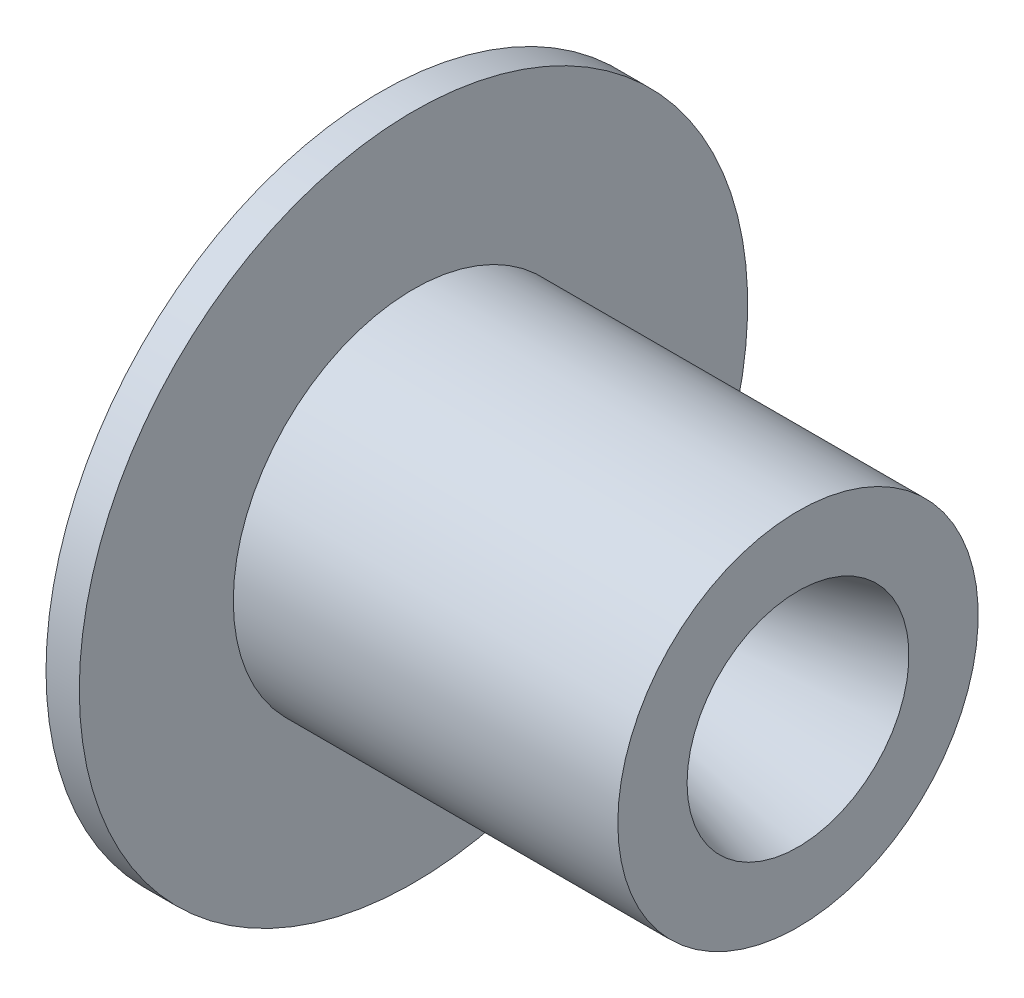
SolidWorks part; units mm, degrees
ref_plane "Front Plane" through (0, 0, 0) normal (0, 0, 1) x (1, 0, 0)
ref_plane "Top Plane" through (0, 0, 0) normal (0, 1, 0) x (1, 0, 0)
ref_plane "Right Plane" through (0, 0, 0) normal (1, 0, 0) x (0, 0, -1)
sketch "Sketch1" plane through (0, 0, 0) normal (0, 0, 1) x (1, 0, 0)
  line L20 (-1.458, 2.4752) -> (32.997, 2.4752) construction
  line L33 (20, 9.4212) -> (26.5, 9.4212)
  line L34 (20, 9.4212) -> (0, 27.8752)
  line L37 (0, 27.8752) -> (0, 53.4752)
  line L38 (0, 53.4752) -> (5.08, 53.4752)
  line L39 (5.08, 53.4752) -> (5.08, 29.9752)
  line L43 (63.7608, 29.9752) -> (63.7608, 19.4052)
  line L52 (63.7608, 19.4052) -> (26.5, 9.4212)
  line L53 (63.7608, 29.9752) -> (5.08, 29.9752)
  point P0 (-1.458, 2.4752)
  point P1 (2.54, 53.4752)
  point P12 (20, 9.4212)
  point P24 (26.5, 9.4212)
  dimension "D1" = 6.946
  dimension "D2" = 25.4
  dimension "D5" = 5.08
  dimension "D7" = 20
  dimension "D10" = 15
  dimension "D8" = 16.93
  dimension "D3" = 27.5
  dimension "D4" = 51
  dimension "D6" = 6.5
revolve "Nozzle" add sketch "Sketch1" angle 360 about L20
sketch "Sketch3" plane through (0, 0, 0) normal (-1, 0, 0) x (0, 0, 1)
  circle A0 centre (0, 42.4802) radius 3.3
  circle A1 centre (0, 2.4752) radius 51 construction
  circle A2 centre (28.2878, 30.763) radius 3.3
  circle A3 centre (40.005, 2.4752) radius 3.3
  circle A4 centre (28.2878, -25.8126) radius 3.3
  circle A5 centre (0, -37.5298) radius 3.3
  circle A6 centre (-28.2878, -25.8126) radius 3.3
  circle A7 centre (-40.005, 2.4752) radius 3.3
  circle A8 centre (-28.2878, 30.763) radius 3.3
  circle A13 centre (0, 2.4752) radius 32.6265 construction
  point P6 (0, 2.4752)
  point P29 (0, 2.4752)
  dimension "D1" = 6.6
  dimension "D2" = 40.005
  dimension "D3" = 8
fillet "Rao inlet radius" radius 20.8 1 edges at (26.5, 2.4752, 6.946)
fillet "Rao outlet radius" radius 5.3067 1 edges at (20, 2.4752, 6.946)
equation "\"radius\"= 1in"
equation "\"Flange\"= 2.35cm"
equation "\"Length\"= 2cm"
equation "\"Flange_Thickness\"= 0.2in"
equation "\"offset\"= 0.625cm"
equation "\"D2@Sketch1\"=\"radius\""
equation "\"throat\"= 0.6946cm"
equation "\"hole_dia\"= 0.66cm"
equation "\"D1@Sketch1\"=\"throat\""
equation "\"D5@Sketch1\"=\"Flange_Thickness\""
equation "\"D7@Sketch1\"=\"Length\""
equation "\"D1@Sketch3\"=\"hole_dia\""
equation "\"D2@Sketch3\"=1.575in"
equation "\"Seal_dia\"= 2.5cm"
equation "\"Seal_depth\"= 0.1cm"
equation "\"Seal_width\"= 0.15cm"
equation "\"Nozzle_angle\"= 15"
equation "\"D10@Sketch1\"=\"Nozzle_angle\""
equation "\"nozzle_length\"= 6.34"
equation "\"bolt_head_dia\"=2.3795"
equation "\"bolt_rad\"= \"radius\" + 0.5 * \"Flange\" + ( ( \"offset\" ^ 2 ) - ( \"Flange_Thickness\" ^ 2 ) ) ^ 0.5cm"
equation "\"scallop_inner_dia\"= 3.3in"
equation "\"exit_rad\"= 1.693cm"
equation "\"D8@Sketch1\"=\"exit_rad\""
equation "\"outside_dia\"= 2.75cm"
equation "\"D3@Sketch1\"=\"outside_dia\""
equation "\"D4@Sketch1\"=\"outside_dia\"+\"Flange\""
equation "\"Scallop_OD\"= 0.8in"
equation "\"D1@Rao outlet radius\" = 2 * 0.382 * \"throat\""
equation "\"D3@Sketch5\"=\"Scallop_OD\"/2"
equation "\"D4@Sketch5\"=\"scallop_inner_dia\"/2"
